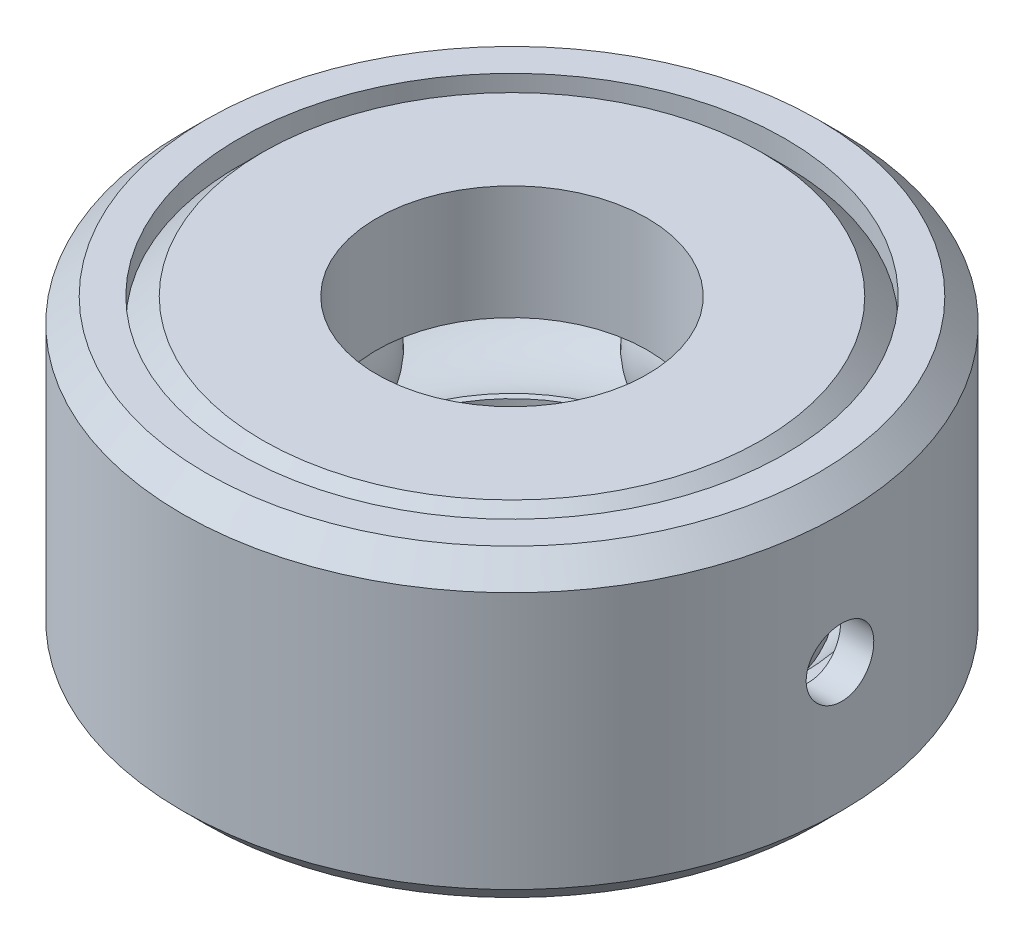
SolidWorks part; units mm, degrees
ref_plane "Front Plane" through (0, 0, 0) normal (0, 0, 1) x (1, 0, 0)
ref_plane "Top Plane" through (0, 0, 0) normal (0, 1, 0) x (1, 0, 0)
ref_plane "Right Plane" through (0, 0, 0) normal (1, 0, 0) x (0, 0, -1)
sketch "Sketch1" plane through (0, 0, 0) normal (1, 0, 0) x (0, 0, -1)
  line L0 (-10.1402, 0) -> (10.1402, 0) construction
  line L1 (0, -7.1438) -> (0, 7.1437) construction
  line L2 (-11.711, 7.1437) -> (-6.35, 7.1437)
  line L3 (-13.2335, 1.7859) -> (-13.9303, 1.7859)
  line L4 (-13.9303, 1.7859) -> (-13.9303, 4.9245)
  line L5 (-13.9303, 4.9245) -> (-11.711, 7.1437)
  line L6 (-6.35, 7.1437) -> (-6.35, 1.7859)
  line L7 (-6.35, 1.7859) -> (-7.0468, 1.7859)
  line L8 (-10.1402, 3.5719) -> (-10.1402, 0) construction
  line L9 (-13.712, 0) -> (-15.4781, 0) construction
  line L10 (-6.7437, -7.1437) -> (-6.7437, -1.7859)
  line L11 (-6.7437, -1.7859) -> (-7.0468, -1.7859)
  line L12 (-13.2335, -1.7859) -> (-13.9303, -1.7859)
  line L13 (-13.9303, -1.7859) -> (-13.9303, -4.9245)
  line L14 (-13.9303, -4.9245) -> (-11.711, -7.1437)
  line L15 (-11.711, -7.1437) -> (-6.7437, -7.1437)
  circle A0 centre (-10.1402, 0) radius 3.5719 construction
  arc A1 (-7.0468, 1.7859) -> (-13.2335, 1.7859) centre (-10.1402, 0) ccw
  arc A2 (-7.0468, -1.7859) -> (-13.2335, -1.7859) centre (-10.1402, 0) cw
  point P15 (-10.1402, 1.7859)
  dimension "D2" = 7.1437
  dimension "Shaft Dia" = 12.7
  dimension "Th" = 14.2875
  dimension "D1" = 45
  dimension "OD" = 30.9562
  dimension "D3" = 27.8606
  dimension "Shaft Dia 2" = 13.4874
revolve "Revolve1" add sketch "Sketch1" angle 360 about L1
sketch "Sketch3" plane through (0, 0, 0) normal (1, 0, 0) x (0, 0, -1)
  line L0 (-10.1402, 3.5719) -> (-10.1402, -3.5719)
  arc A0 (-13.2335, -1.7859) -> (-7.0468, -1.7859) centre (-10.1402, 0) ccw construction
  arc A1 (-10.1402, 3.5719) -> (-10.1402, -3.5719) centre (-10.1402, 0) ccw
revolve "Revolve2" add sketch "Sketch3" angle 360 about L0
ref_axis "Axis1" through (0, 7.1437, 0) along (0, -1, 0)
pattern_circular "CirPattern1" count 4 every 90 about axis through (0, 7.1437, 0) along (0, -1, 0) of bodies 171
sketch "Sketch4" plane through (0, 0, 0) normal (1, 0, 0) x (0, 0, -1)
  line L0 (-12.8207, 7.1437) -> (-14.3685, 7.1437)
  line L1 (-14.3685, 7.1437) -> (-15.4781, 6.0341)
  line L2 (-12.8207, -7.1437) -> (-12.8207, -6.0341)
  line L3 (-13.9303, -4.9245) -> (-11.711, -7.1437) construction
  line L4 (-12.8207, -6.0341) -> (-13.9303, -4.9245)
  line L5 (-13.9303, -4.9245) -> (-13.9303, 4.9245)
  line L6 (-13.9303, 4.9245) -> (-12.8207, 6.0341)
  line L7 (-13.9303, 4.9245) -> (-11.711, 7.1437) construction
  line L8 (-12.8207, 6.0341) -> (-12.8207, 7.1437)
  line L9 (-15.4781, 6.0341) -> (-15.4781, -6.0341)
  line L10 (-15.4781, -6.0341) -> (-14.3685, -7.1437)
  line L11 (-14.3685, -7.1437) -> (-12.8207, -7.1437)
  line L12 (-11.711, 7.1437) -> (-6.35, 7.1437) construction
  line L13 (-11.711, -7.1437) -> (-6.7437, -7.1437) construction
revolve "Revolve3" add sketch "Sketch4" angle 360 about L1
sketch "Sketch5" plane through (0, 0, 0) normal (1, 0, 0) x (0, 0, -1)
  circle A0 centre (0, 0) radius 1.5875
  dimension "D1" = 3.175
extrude "Cut-Extrude1" cut sketch "Sketch5" along normal through all
sketch "Sketch6" plane through (0, 0, 0) normal (1, 0, 0) x (0, 0, -1)
  line L0 (0, 0) -> (0, 7.1438) construction
  line L1 (14.3685, 7.1437) -> (-14.3685, 7.1437) construction
  line L2 (11.711, -7.1437) -> (6.7437, -7.1437)
  line L3 (13.9303, -4.9245) -> (11.711, -7.1437)
  line L4 (13.9303, -1.7859) -> (13.9303, -4.9245)
  line L5 (13.2335, -1.7859) -> (13.9303, -1.7859)
  line L6 (-6.35, 7.1437) -> (-11.711, 7.1437)
  line L7 (-6.35, 1.7859) -> (-6.35, 7.1437)
  line L8 (-7.0468, 1.7859) -> (-6.35, 1.7859)
  line L9 (-13.9303, 1.7859) -> (-13.2335, 1.7859)
  line L10 (-13.9303, 4.9245) -> (-13.9303, 1.7859)
  line L11 (-11.711, 7.1437) -> (-13.9303, 4.9245)
  line L12 (-6.35, 7.1437) -> (-11.711, 7.1437)
  line L13 (-6.35, 1.7859) -> (-6.35, 7.1437)
  line L14 (-7.0468, 1.7859) -> (-6.35, 1.7859)
  line L15 (-13.9303, 1.7859) -> (-13.2335, 1.7859)
  line L16 (-13.9303, 4.9245) -> (-13.9303, 1.7859)
  line L17 (-11.711, 7.1437) -> (-13.9303, 4.9245)
  line L18 (-6.7437, -7.1437) -> (-6.7437, -1.7859)
  line L19 (-6.7437, -1.7859) -> (-7.0468, -1.7859)
  line L20 (-13.2335, -1.7859) -> (-13.9303, -1.7859)
  line L21 (-13.9303, -1.7859) -> (-13.9303, -4.9245)
  line L22 (-13.9303, -4.9245) -> (-11.711, -7.1437)
  line L23 (-11.711, -7.1437) -> (-6.7437, -7.1437)
  line L24 (-6.7437, -7.1437) -> (-6.7437, -1.7859)
  line L25 (-6.7437, -1.7859) -> (-7.0468, -1.7859)
  line L26 (-13.2335, -1.7859) -> (-13.9303, -1.7859)
  line L27 (-13.9303, -1.7859) -> (-13.9303, -4.9245)
  line L28 (-13.9303, -4.9245) -> (-11.711, -7.1437)
  line L29 (-11.711, -7.1437) -> (-6.7437, -7.1437)
  line L30 (6.7437, -1.7859) -> (7.0468, -1.7859)
  line L31 (6.7437, -7.1437) -> (6.7437, -1.7859)
  line L32 (11.711, 7.1437) -> (13.9303, 4.9245)
  line L33 (13.9303, 4.9245) -> (13.9303, 1.7859)
  line L34 (13.9303, 1.7859) -> (13.2335, 1.7859)
  line L35 (7.0468, 1.7859) -> (6.35, 1.7859)
  line L36 (6.35, 1.7859) -> (6.35, 7.1437)
  line L37 (6.35, 7.1437) -> (11.711, 7.1437)
  line L38 (-6.35, 1.7859) -> (6.35, 1.7859)
  line L39 (-6.35, 7.1437) -> (6.35, 7.1437)
  line L40 (-6.7437, -7.1437) -> (6.7437, -7.1437)
  line L41 (-6.7437, -1.7859) -> (6.7437, -1.7859)
  arc A0 (13.2335, -1.7859) -> (7.0468, -1.7859) centre (10.1402, 0) cw
  arc A1 (-7.0468, 1.7859) -> (-13.2335, 1.7859) centre (-10.1402, 0) ccw
  arc A2 (-7.0468, 1.7859) -> (-13.2335, 1.7859) centre (-10.1402, 0) ccw
  arc A3 (-13.2335, -1.7859) -> (-7.0468, -1.7859) centre (-10.1402, 0) ccw
  arc A4 (-13.2335, -1.7859) -> (-7.0468, -1.7859) centre (-10.1402, 0) ccw
  arc A5 (7.0468, 1.7859) -> (13.2335, 1.7859) centre (10.1402, 0) cw
  dimension "D1" = 0
  dimension "D2" = 0
ref_axis "Center Axis 1" through (0, -7.1438, 0) along (0, 1, 0)
ref_plane "Contact Plane 1" through (0, -9.6837, 0) normal (0, -1, 0) x (-1, 0, 0)
ref_plane "Contact Plane 2" through (0, 9.6837, 0) normal (0, 1, 0) x (1, 0, 0)
equation "\"D2@Sketch1\" = \"Th@Sketch1\"/2"
equation "\"Balls@CirPattern1\" = \"OD@Sketch1\"*3"
equation "\"Angle@CirPattern1\" = 360/\"Balls@CirPattern1\""
equation "\"D3@Sketch1\" = \"OD@Sketch1\"*.9"
